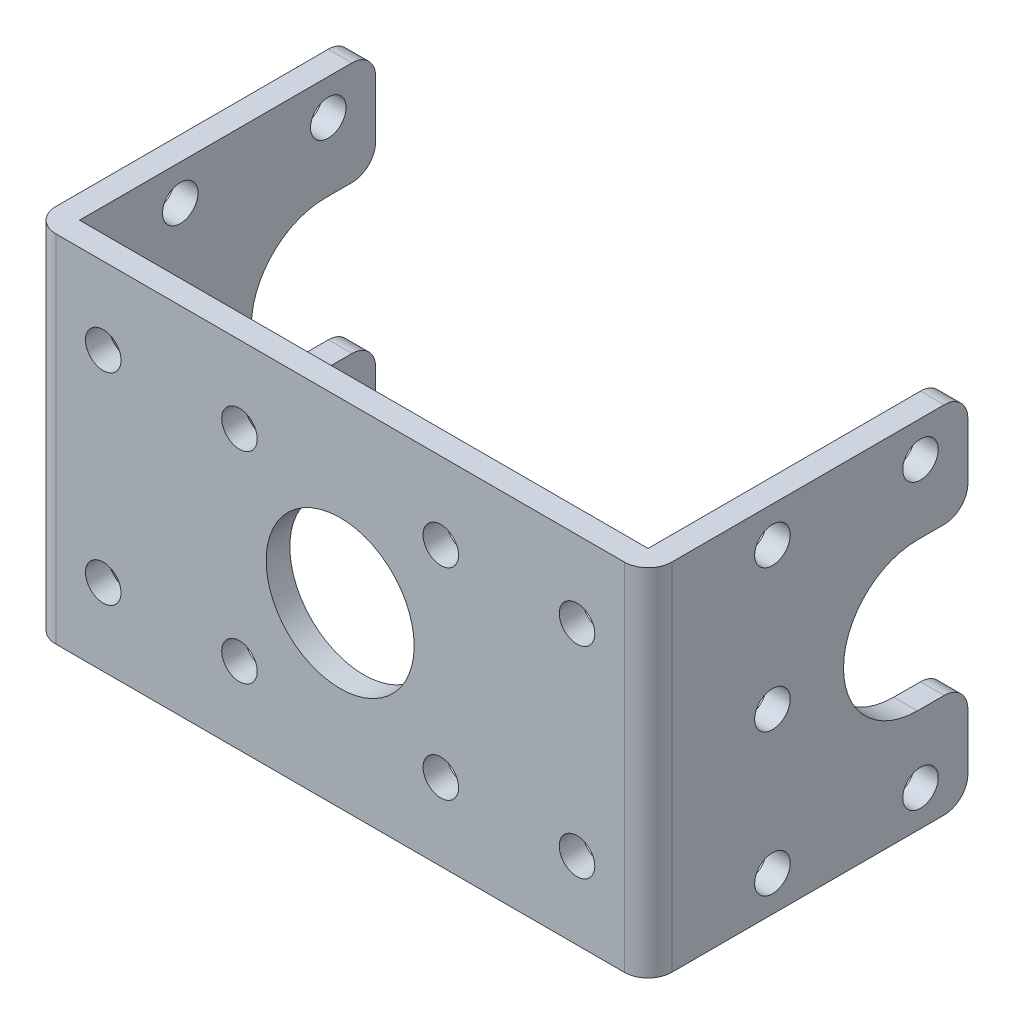
SolidWorks part; units mm, degrees
ref_plane "Front Plane" through (0, 0, 0) normal (0, 0, 1) x (1, 0, 0)
ref_plane "Top Plane" through (0, 0, 0) normal (0, 1, 0) x (1, 0, 0)
ref_plane "Right Plane" through (0, 0, 0) normal (1, 0, 0) x (0, 0, -1)
sketch "Sketch1" plane through (0, 0, 0) normal (0, 1, 0) x (1, 0, 0)
  line L0 (-24, 0) -> (24, 0) construction
  line L1 (24, 0) -> (24, -25)
  line L2 (24, -25) -> (-24, -25)
  line L3 (-24, -25) -> (-24, 0)
  line L4 (-24, 0) -> (-26, 0)
  line L5 (-26, 0) -> (-26, -27)
  line L6 (24, 0) -> (26, 0)
  line L7 (26, 0) -> (26, -27)
  line L8 (26, -27) -> (-26, -27)
  point P4 (0, 0)
  dimension "D1" = 2
  dimension "D2" = 2
  dimension "D3" = 2
  dimension "D4" = 48
  dimension "D5" = 25
extrude "Boss-Extrude1" add sketch "Sketch1" along normal blind 30
sketch "Sketch2" plane through (26, 0, 0) normal (1, 0, 0) x (0, 0, -1)
  line L0 (0, 15) -> (-10.5, 15) construction
  line L1 (0, 30) -> (0, 0) construction
  line L2 (-4, 27) -> (-4, 3) construction
  line L4 (-4.25, 21.25) -> (0, 21.25)
  line L5 (-4.25, 8.75) -> (0, 8.75)
  line L6 (0, 21.25) -> (0, 8.75)
  line L8 (-4, 27) -> (0, 27) construction
  line L11 (-10.5, 15) -> (-16.5, 15) construction
  arc A0 (-4.25, 21.25) -> (-4.25, 8.75) centre (-4.25, 15) ccw
  circle A1 centre (-4, 27) radius 1.5
  circle A2 centre (-4, 3) radius 1.5
  circle A3 centre (-16.5, 15) radius 1.5
  circle A4 centre (-16.5, 27) radius 1.5
  circle A5 centre (-16.5, 3) radius 1.5
  point P8 (-4, 15)
extrude "Cut-Extrude1" cut sketch "Sketch2" against normal through all
sketch "Sketch3" plane through (0, 0, 27) normal (0, 0, 1) x (1, 0, 0)
  line L0 (0, 0) -> (0, 30) construction
  line L1 (-26, 0) -> (26, 0) construction
  line L2 (-26, 30) -> (26, 30) construction
  line L3 (-8.5, 15) -> (8.5, 15) construction
  line L4 (8.5, 23.5) -> (8.5, 6.5) construction
  line L5 (8.5, 23.5) -> (20, 23.5) construction
  line L6 (8.5, 6.5) -> (20, 6.5) construction
  line L7 (-8.5, 23.5) -> (-8.5, 6.5) construction
  line L8 (-8.5, 6.5) -> (-20, 6.5) construction
  line L9 (-8.5, 23.5) -> (-20, 23.5) construction
  circle A0 centre (0, 15) radius 6.25
  circle A1 centre (20, 23.5) radius 1.5
  circle A2 centre (20, 6.5) radius 1.5
  circle A3 centre (8.5, 6.5) radius 1.5
  circle A4 centre (8.5, 23.5) radius 1.5
  circle A5 centre (-8.5, 6.5) radius 1.5
  circle A6 centre (-20, 6.5) radius 1.5
  circle A7 centre (-8.5, 23.5) radius 1.5
  circle A8 centre (-20, 23.5) radius 1.5
  point P11 (8.5, 15)
  dimension "D1" = 8.5
extrude "Cut-Extrude2" cut sketch "Sketch3" against normal blind 30
fillet "Fillet1" radius 2 10 edges at (-25, 21.25, 0) (-25, 30, 0) (-25, 8.75, 0) (-25, 0, 0) (25, 0, 0) (25, 8.75, 0) (25, 21.25, 0) (25, 30, 0) (26, 15, 27) (-26, 15, 27)
